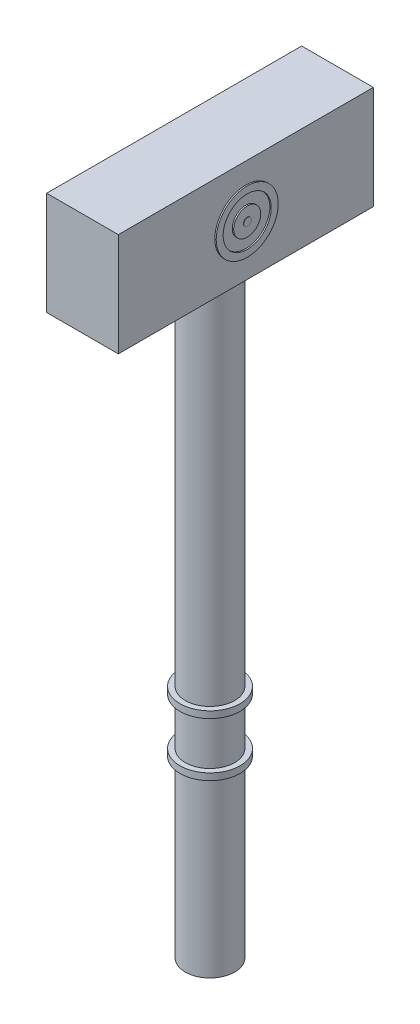
SolidWorks part; units mm, degrees
ref_plane "Front Plane" through (0, 0, 0) normal (0, 0, 1) x (1, 0, 0)
ref_plane "Top Plane" through (0, 0, 0) normal (0, 1, 0) x (1, 0, 0)
ref_plane "Right Plane" through (0, 0, 0) normal (1, 0, 0) x (0, 0, -1)
sketch "Sketch2" plane through (0, 10, 0) normal (0, 1, 0) x (1, 0, 0)
  circle A0 centre (0, 0) radius 31.75
  circle A1 centre (0, 0) radius 36.75
  dimension "D1" = 63.5
  dimension "D2" = 5
extrude "Boss-Extrude2" add sketch "Sketch2" along normal blind 900
sketch "Sketch4" plane through (0, 0, 0) normal (0, 0, 1) x (1, 0, 0)
  line L0 (-125, 10) -> (-125, 37.1237)
  line L1 (-125, 37.1237) -> (-87.8079, 71.9735)
  line L2 (-87.8079, 71.9735) -> (-36.75, 71.9735)
  line L3 (-36.75, 910) -> (-36.75, 10) construction
  line L4 (-36.75, 71.9735) -> (-36.75, 10)
  line L5 (-36.75, 10) -> (-125, 10)
extrude "Boss-Extrude10" add sketch "Sketch4" along normal mid plane 10 separate body
pattern_circular "CirPattern3" count 4 over 360 of bodies 104
ref_plane "Plane1" through (0, 280, 0) normal (0, 1, 0) x (1, 0, 0)
sketch "Sketch5" plane through (0, 280, 0) normal (0, 1, 0) x (1, 0, 0)
  circle A0 centre (0, 0) radius 36.75 construction
  circle A1 centre (0, 0) radius 36.75
  circle A2 centre (0, 0) radius 44.75
  dimension "D1" = 8
extrude "Boss-Extrude11" add sketch "Sketch5" against normal blind 10
ref_axis "Axis1" through (0, 910, 0) along (0, -1, 0)
pattern_linear "LPattern1" count 2 spacing 80 along (0, 1, 0) of "Boss-Extrude11"
delete or keep bodies "Body-Delete/Keep 1" bodies 106 105 104 107
sketch "Sketch6" plane through (0, 0, 0) normal (1, 0, 0) x (0, 0, -1)
  line L0 (-36.75, 910) -> (-189.7686, 910)
  line L1 (-189.7686, 910) -> (-189.7686, 1063.7465)
  line L2 (-189.7686, 1063.7465) -> (189.7686, 1063.7465)
  line L3 (189.7686, 1063.7465) -> (189.7686, 910)
  line L4 (189.7686, 910) -> (36.75, 910)
  line L5 (-36.75, 910) -> (36.75, 910)
extrude "Boss-Extrude12" add sketch "Sketch6" along normal mid plane 106.68
sketch "Sketch7" plane through (0, 0, 0) normal (1, 0, 0) x (0, 0, -1)
  circle A0 centre (0, 986.6508) radius 46.1383
  circle A1 centre (0, 986.6508) radius 35.802
  circle A2 centre (0, 986.6508) radius 15.4908 construction
extrude "Boss-Extrude15" add sketch "Sketch7" along normal blind 55.372
sketch "Sketch8" plane through (0, 0, 0) normal (1, 0, 0) x (0, 0, -1)
  circle A0 centre (0, 986.6508) radius 20.1434
extrude "Boss-Extrude16" add sketch "Sketch8" along normal blind 55.372
sketch "Sketch9" plane through (0, 0, 0) normal (1, 0, 0) x (0, 0, -1)
  circle A0 centre (0, 986.6508) radius 5.6633
extrude "Boss-Extrude18" add sketch "Sketch9" along normal blind 55.88
scale "Scale1" scale about origin uniform scaling yes scale factor 0.1
